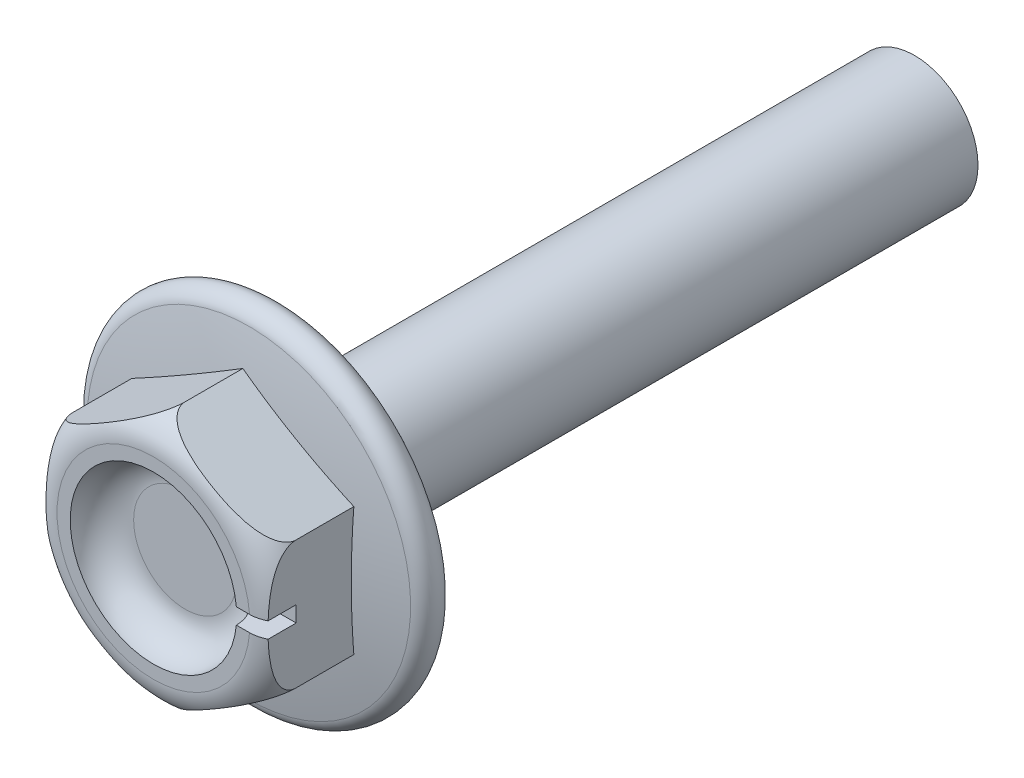
SolidWorks part; units mm, degrees
extrude "Shank" add sketch "Shank Sketch" against normal blind 20
sketch "Shank Sketch" plane through (0, 0, 0) normal (0, 0, 1) x (1, 0, 0)
  line L0 (50, 0) -> (-50, 0) construction
  line L1 (0, -50) -> (0, 50) construction
  circle A0 centre (0, 0) radius 2
  dimension "Shank diameter" = 4
extrude "Head" add sketch "Head Sketch" along normal blind 4
sketch "Head Sketch" plane through (0, 0, 0) normal (0, 0, 1) x (1, 0, 0)
  line L0 (0, 4.0415) -> (3.5, 2.0207)
  line L1 (3.5, 2.0207) -> (3.5, -2.0207)
  line L2 (3.5, -2.0207) -> (0, -4.0415)
  line L3 (0, -4.0415) -> (-3.5, -2.0207)
  line L4 (-3.5, -2.0207) -> (-3.5, 2.0207)
  line L5 (-3.5, 2.0207) -> (0, 4.0415)
  line L6 (3.5, 2.0207) -> (-3.5, -2.0207) construction
  line L7 (0, 4.0415) -> (0, -4.0415) construction
  line L8 (-3.5, 2.0207) -> (3.5, -2.0207) construction
  point P0 (0, 0)
  dimension "D1" = 60
  dimension "D2" = 60
  dimension "Width across flats" = 7
ref_plane "Plane1" through (0, 0, 0) normal (0, 0, 1) x (1, 0, 0)
ref_plane "Plane2" through (0, 0, 0) normal (0, 1, 0) x (-1, 0, 0)
ref_plane "Plane3" through (0, 0, 0) normal (1, 0, 0) x (0, 0, -1)
other "Configuration Table"
sketch "Sketch3" plane through (0, 0, 0) normal (0, 1, 0) x (-1, 0, 0)
  line L0 (0, 0) -> (0, 3) construction
  line L1 (0, -20) -> (0, 0) construction
  line L4 (-5, 0) -> (0, 0)
  line L5 (0, 0) -> (0, 1.5)
  arc A0 (0, 1.5) -> (-5.099, 0.9901) centre (0, -24.25) ccw
  arc A1 (-5, 0) -> (-5.099, 0.9901) centre (-5, 0.5) cw
  dimension "D1" = 0.5
  dimension "D2" = 10
  dimension "D3" = 1.5
revolve "Flange" add sketch "Sketch3" angle 360 about L0
sketch "Sketch5" plane through (0, 0, 0) normal (1, 0, 0) x (0, 0, -1)
  line L0 (-4, -3.0415) -> (-4, -4.0415)
  line L1 (-4, -4.0415) -> (-3, -4.0415)
  line L2 (-4, -4.0415) -> (-1.1809, -4.0415) construction
  line L3 (-4, -4.0415) -> (-4, -2.0207) construction
  line L5 (-15.0856, 0) -> (-8.1394, 0) construction
  line L6 (50, 0) -> (-50, 0) construction
  arc A0 (-4, -3.0415) -> (-3, -4.0415) centre (-3, -3.0415) ccw
  dimension "D1" = 1
revolve "Head Trim" cut sketch "Sketch5" angle 360 about L5
sketch "Sketch6" plane through (0, 0, 4) normal (0, 0, 1) x (1, 0, 0)
  circle A3 centre (0, 0) radius 2.625
  dimension "D1" = 5.25
extrude "Head Cut" cut sketch "Sketch6" against normal blind 1
fillet "Fillet1" radius 1 1 edges at (2.625, 0, 3)
sketch "Sketch8" plane through (0, 0, 4) normal (0, 0, 1) x (1, 0, 0)
  line L0 (0, 0) -> (3.5, 0) construction
  line L1 (3.5, -2.0207) -> (3.5, 2.0207) construction
  line L2 (0, 0.25) -> (0, -0.25)
  line L3 (0, -0.25) -> (3.5, -0.25)
  line L4 (3.5, -2.0207) -> (3.5, 2.0207) construction
  line L5 (0, 0.25) -> (3.5, 0.25)
  line L6 (3.5, -0.25) -> (3.5, 0.25)
  circle A0 centre (0, 0) radius 1.625 construction
  dimension "D1" = 0.5
extrude "Cut-Extrude3" cut sketch "Sketch8" against normal blind 1
equation "\"D1@Sketch6\" = \"Width across flats@Head Sketch\"*3/4"
